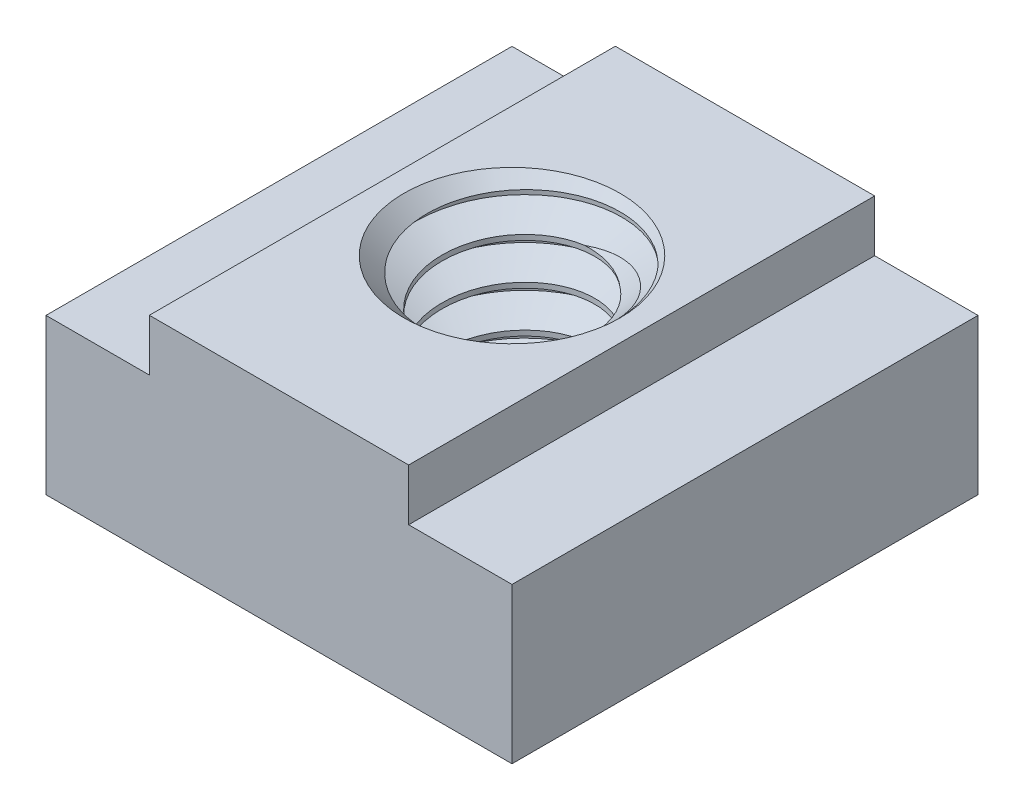
SolidWorks part; units mm, degrees
ref_plane "Front Plane" through (0, 0, 0) normal (0, 0, 1) x (1, 0, 0)
ref_plane "Top Plane" through (0, 0, 0) normal (0, 1, 0) x (1, 0, 0)
ref_plane "Right Plane" through (0, 0, 0) normal (1, 0, 0) x (0, 0, -1)
sketch "Sketch1" plane through (0, 0, 0) normal (0, 0, 1) x (1, 0, 0)
  line L0 (-7.1438, 0) -> (7.1438, 0) construction
  line L1 (7.1438, 0) -> (7.1438, 4.7625) construction
  line L2 (7.1438, 4.7625) -> (3.9751, 4.7625) construction
  line L3 (3.9751, 4.7625) -> (3.9751, 6.35) construction
  line L4 (3.9751, 6.35) -> (-3.9751, 6.35) construction
  line L5 (-3.9751, 6.35) -> (-3.9751, 4.7625) construction
  line L6 (-3.9751, 4.7625) -> (-7.1438, 4.7625) construction
  line L7 (-7.1438, 4.7625) -> (-7.1438, 0) construction
  line L8 (-3.175, 6.35) -> (3.175, 6.35) construction
  line L9 (3.175, 6.35) -> (3.175, 0) construction
  line L10 (-3.175, 6.35) -> (-3.175, 0) construction
  line L11 (3.3125, 7.5406) -> (3.3125, 6.2706) construction
  line L12 (3.3125, 6.2706) -> (2.2126, 6.9056) construction
  line L13 (2.2126, 6.9056) -> (3.3125, 7.5406) construction
  line L14 (2.2126, 6.9056) -> (2.3501, 6.9056) construction
  line L15 (2.3501, 6.985) -> (2.3501, 6.8262) construction
  line L16 (3.3125, 6.9056) -> (3.175, 6.9056) construction
  line L17 (3.175, 6.35) -> (3.175, 7.4612) construction
  line L18 (3.2437, 6.9056) -> (3.2437, 7.5009) construction
  line L19 (3.2437, 6.9056) -> (3.2437, 6.3103) construction
  point P8 (0, 0)
  point P9 (0, 6.35)
  point P14 (0, 6.35)
  dimension "Base Width" = 14.2875
  dimension "Base Height" = 4.7625
  dimension "For Slot Width" = 7.9502
  dimension "Overall Height" = 6.35
  dimension "Thread Diameter" = 6.35
  dimension "Pitch" = 1.27
  dimension "D5" = 0.1588
sketch "Sketch2" plane through (0, 0, 0) normal (1, 0, 0) x (0, 0, -1)
  line L1 (-7.1437, 0) -> (7.1437, 0) construction
  line L2 (-7.1437, 0) -> (-7.1437, 6.35) construction
  line L3 (-7.1437, 6.35) -> (7.1438, 6.35) construction
  line L4 (7.1437, 0) -> (7.1438, 6.35) construction
  point P5 (0, 0)
  point P9 (0, 6.35)
  dimension "Length" = 14.2875
ref_plane "Plane1" through (0, 6.35, 0) normal (0, 1, 0) x (1, 0, 0)
sketch "Sketch3" plane through (0, 0, 0) normal (0, 0, 1) x (1, 0, 0)
  line L0 (-7.1438, 0) -> (-7.1438, 4.7625)
  line L1 (-7.1438, 4.7625) -> (-3.9751, 4.7625)
  line L2 (-3.9751, 4.7625) -> (-3.9751, 6.35)
  line L3 (-3.9751, 6.35) -> (3.9751, 6.35)
  line L4 (3.9751, 6.35) -> (3.9751, 4.7625)
  line L5 (3.9751, 4.7625) -> (7.1438, 4.7625)
  line L6 (7.1438, 4.7625) -> (7.1438, 0)
  line L7 (7.1438, 0) -> (-7.1438, 0)
extrude "Boss-Extrude1" add sketch "Sketch3" along normal up to vertex (7.1437 mm away) from vertex at -7.1437 starting at point (0, 6.35, -7.1438)
sketch "Sketch4" plane through (0, 0, 0) normal (0, 1, 0) x (1, 0, 0)
  circle A0 centre (0, 0) radius 3.175
extrude "Cut-Extrude2" cut sketch "Sketch4" along normal through all
sketch "Sketch6" plane through (0, 0, 0) normal (0, 0, 1) x (1, 0, 0)
  line L0 (3.2437, 7.5009) -> (3.2437, 6.3103)
  line L1 (3.2437, 6.3103) -> (2.3501, 6.8262)
  line L2 (2.3501, 6.8262) -> (2.3501, 6.985)
  line L3 (2.3501, 6.985) -> (3.2437, 7.5009)
sketch "Sketch7" plane through (0, 6.35, 0) normal (0, 1, 0) x (1, 0, 0)
  circle A0 centre (0, 0) radius 3.175
curve "Helix/Spiral1" pitch 1.27 height 7.62 turns 6
sweep "Sweep1" add profiles "Sketch6" path "Helix/Spiral1"
sketch "Sketch8" plane through (0, 0, 0) normal (0, 1, 0) x (1, 0, 0)
  circle A0 centre (0, 0) radius 3.3125
extrude "Cut-Extrude3" cut sketch "Sketch8" along normal through all draft 45 and the other way through all draft 45
sketch "Sketch9" plane through (0, 6.35, 0) normal (0, 1, 0) x (1, 0, 0)
  circle A0 centre (0, 0) radius 3.3125
extrude "Cut-Extrude4" cut sketch "Sketch9" against normal through all draft 45 and the other way through all draft 45
equation "\"D5@Sketch1\"=\"Pitch@Sketch1\"/8"
equation "\"D3@Helix/Spiral1\"=\"Overall Height@Sketch1\"+\"Pitch@Sketch1\""
equation "\"D4@Helix/Spiral1\"=\"Pitch@Sketch1\""
